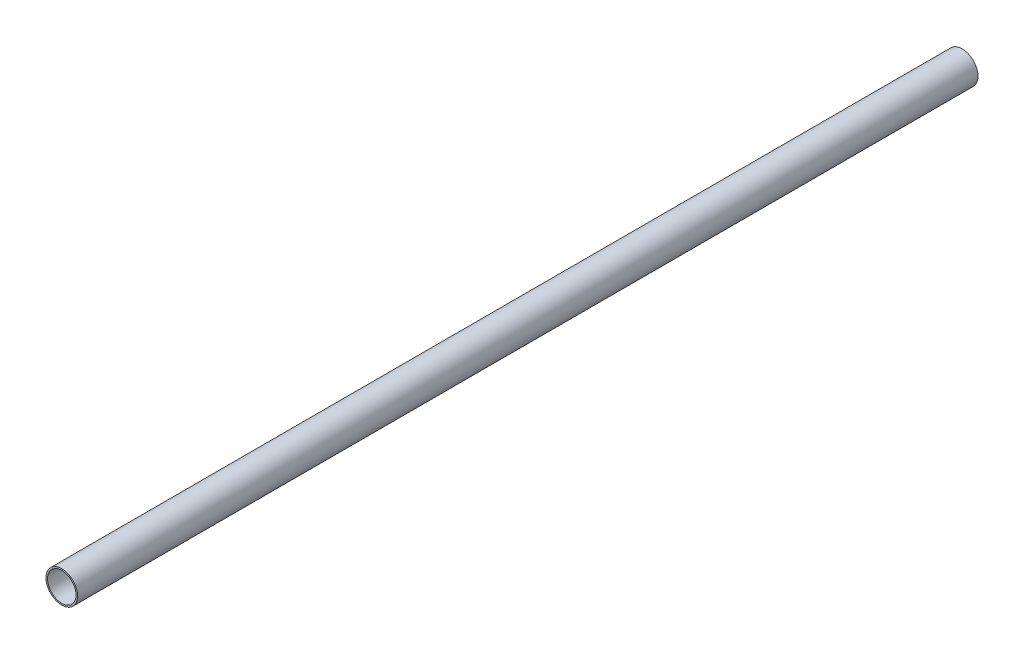
SolidWorks part; units mm, degrees
ref_plane "Front Plane" through (0, 0, 0) normal (0, 0, 1) x (1, 0, 0)
ref_plane "Top Plane" through (0, 0, 0) normal (0, 1, 0) x (1, 0, 0)
ref_plane "Right Plane" through (0, 0, 0) normal (1, 0, 0) x (0, 0, -1)
sketch "Sketch1" plane through (0, 0, 0) normal (0, 0, 1) x (1, 0, 0)
  circle A0 centre (0, 0) radius 15
  dimension "D1" = 30
extrude "Boss-Extrude1" add sketch "Sketch1" along normal blind 854
sketch "Sketch2" plane through (0, 0, 0) normal (0, 0, -1) x (-1, 0, 0)
  circle A0 centre (0, 0) radius 13.5
  dimension "D1" = 27
extrude "Cut-Extrude1" cut sketch "Sketch2" against normal through all
